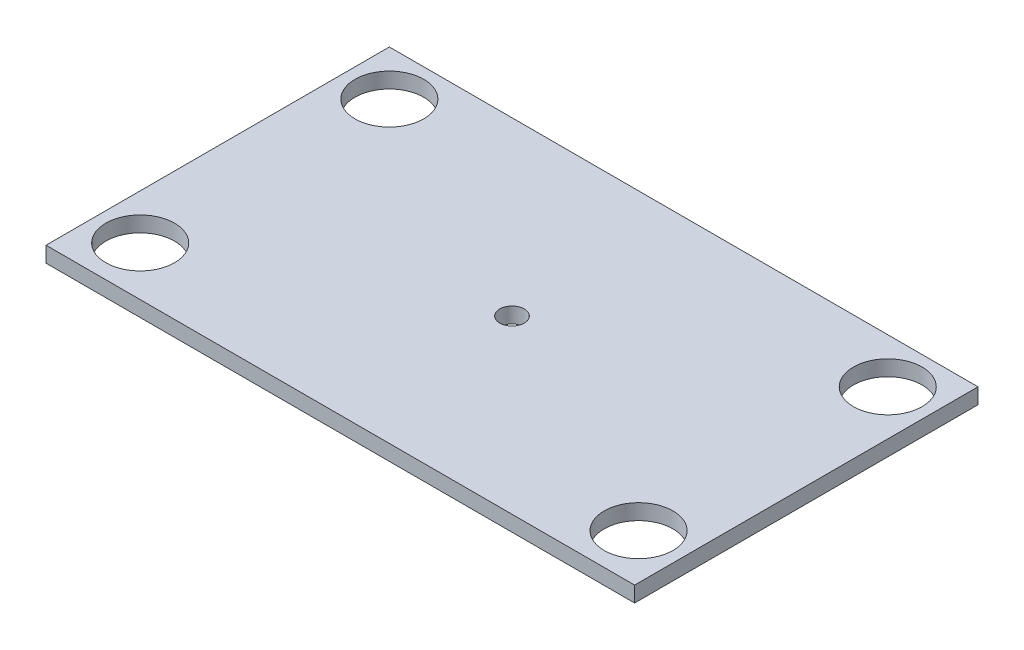
SolidWorks part; units mm, degrees
ref_plane "Front Plane" through (0, 0, 0) normal (0, 0, 1) x (1, 0, 0)
ref_plane "Top Plane" through (0, 0, 0) normal (0, 1, 0) x (1, 0, 0)
ref_plane "Right Plane" through (0, 0, 0) normal (1, 0, 0) x (0, 0, -1)
sketch "Sketch1" plane through (0, 0, 0) normal (0, 1, 0) x (1, 0, 0)
  line L0 (4.6, 30.4) -> (0, 30.4) construction
  line L1 (0, 0) -> (60, 0)
  line L2 (0, 0) -> (0, 35)
  line L3 (0, 35) -> (60, 35)
  line L4 (60, 0) -> (60, 35)
  line L5 (4.6, 30.4) -> (55.4, 30.4) construction
  line L6 (4.6, 30.4) -> (4.6, 5) construction
  line L7 (4.6, 5) -> (55.4, 5) construction
  line L8 (55.4, 30.4) -> (55.4, 5) construction
  line L9 (4.6, 30.4) -> (4.6, 35) construction
  circle A0 centre (4.6, 30.4) radius 3.5
  circle A1 centre (55.4, 30.4) radius 3.5
  circle A2 centre (4.6, 5) radius 3.5
  circle A3 centre (55.4, 5) radius 3.5
  circle A4 centre (30, 17.5) radius 1.25
  point P13 (30, 30.4)
  point P14 (30, 35)
  point P20 (60, 17.5)
  dimension "D5" = 7
  dimension "D6" = 2.5
  dimension "D1" = 60
  dimension "D2" = 35
  dimension "D3" = 50.8
  dimension "D4" = 25.4
extrude "Boss-Extrude1" add sketch "Sketch1" along normal blind 1.5875
